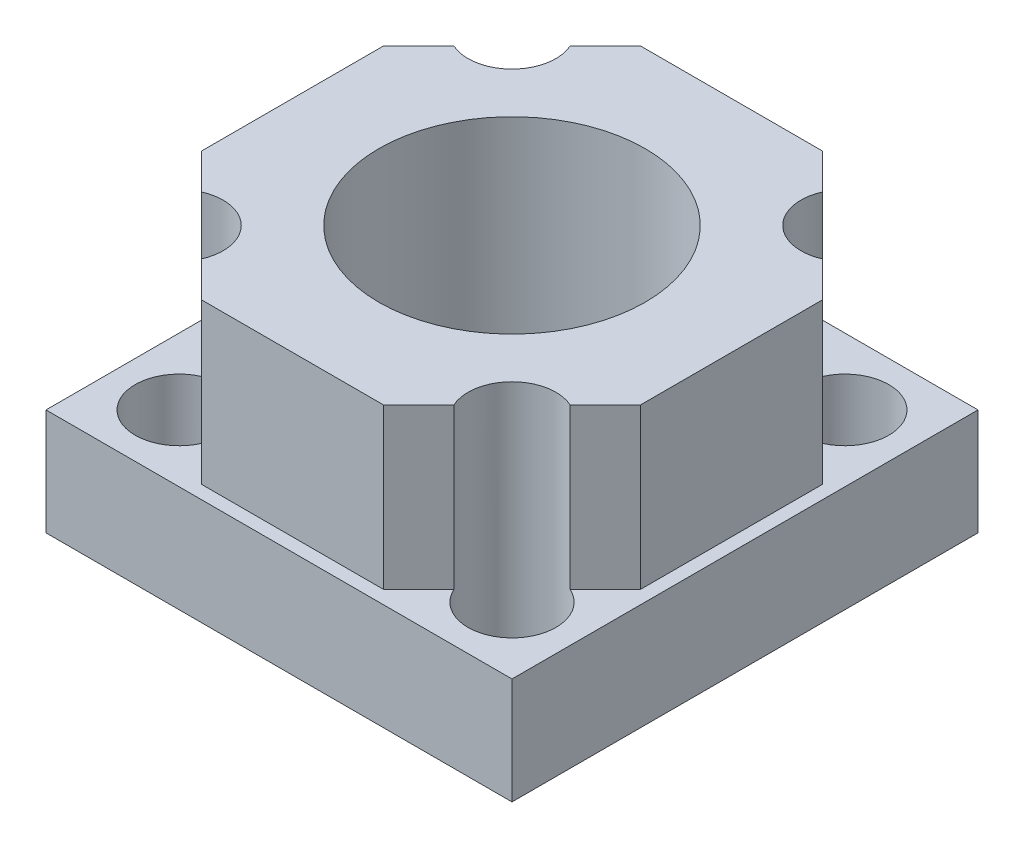
SolidWorks part; units mm, degrees
ref_plane "Front Plane" through (0, 0, 0) normal (0, 0, 1) x (1, 0, 0)
ref_plane "Top Plane" through (0, 0, 0) normal (0, 1, 0) x (1, 0, 0)
ref_plane "Right Plane" through (0, 0, 0) normal (1, 0, 0) x (0, 0, -1)
sketch "Sketch1" plane through (0, 0, 0) normal (0, 1, 0) x (1, 0, 0)
  line L0 (-16.5, -6.8345) -> (-6.8345, -16.5)
  line L1 (-17.5, 17.5) -> (17.5, 17.5)
  line L2 (-17.5, 17.5) -> (-17.5, -17.5)
  line L3 (-17.5, -17.5) -> (17.5, -17.5)
  line L4 (17.5, 17.5) -> (17.5, -17.5)
  line L5 (0, -17.5) -> (0, 17.5) construction
  line L6 (-17.5, 0) -> (17.5, 0) construction
  line L7 (6.8345, -16.5) -> (16.5, -6.8345)
  line L8 (16.5, -6.8345) -> (16.5, 6.8345)
  line L9 (16.5, 6.8345) -> (6.8345, 16.5)
  line L10 (6.8345, 16.5) -> (-6.8345, 16.5)
  line L11 (-6.8345, 16.5) -> (-16.5, 6.8345)
  line L12 (-16.5, 6.8345) -> (-16.5, -6.8345)
  line L13 (-6.8345, -16.5) -> (6.8345, -16.5)
  circle A0 centre (0, 0) radius 16.5 construction
  point P0 (0, 0)
  point P17 (16.5, 0)
  dimension "D1" = 35
  dimension "D2" = 35
  dimension "D3" = 33
extrude "Boss-Extrude1" add sketch "Sketch1" against normal blind 8 contours L0 L13 L7 L8 L9 L10 L11 L12 | L4 L1 L2 L3 L13 L0 L12 L11 L10 L9 L8 L7 region at (0, 0, 0) region at (0, 0, -17.005)
extrude "Boss-Extrude2" add sketch "Sketch1<3>" along normal blind 12 contours L0 L13 L7 L8 L9 L10 L11 L12 region at (0, 0, 0)
sketch "Sketch1<3>" plane through (0, 0, 0) normal (0, 1, 0) x (1, 0, 0) same geometry as "Sketch1"
hole_wizard "M18 Clearance Hole1" positions "Sketch2" profile "Sketch3" hole size "M18" standard "ISO" end condition through all
sketch "Sketch2" plane through (0, 12, 0) normal (0, 1, 0) x (1, 0, 0)
  point P0 (0, 0)
sketch "Sketch3" plane through (0, 12, 0) normal (1, 0, 0) x (0, 0, 1)
  line L0 (0, 0) -> (0, 20)
  line L1 (0, 20) -> (10, 20)
  line L2 (10, 20) -> (10, 0)
  line L5 (10, 0) -> (0, 0)
  line L11 (0, -6.35) -> (0, 107.95) construction
  dimension "Thru Hole Dia." = 20
  dimension "Thru Hole Depth" = 20
hole_wizard "M6 Clearance Hole1" positions "Sketch4" profile "Sketch5" hole size "M6" standard "ISO" end condition through all
sketch "Sketch4" plane through (0, 0, 0) normal (0, 1, 0) x (1, 0, 0)
  line L0 (-17.5, 17.5) -> (-17.5, -17.5) construction
  line L1 (-17.5, 17.5) -> (17.5, 17.5) construction
  point P0 (-12.5, 12.5)
  dimension "D1" = 5
  dimension "D2" = 5
sketch "Sketch5" plane through (-12.5, 0, -12.5) normal (1, 0, 0) x (0, 0, 1)
  line L0 (0, 0) -> (0, 8)
  line L1 (0, 8) -> (3.3, 8)
  line L2 (3.3, 8) -> (3.3, 0)
  line L5 (3.3, 0) -> (0, 0)
  line L11 (0, -6.35) -> (0, 107.95) construction
  dimension "Thru Hole Dia." = 6.6
  dimension "Thru Hole Depth" = 8
sketch "Sketch6" plane through (0, 0, 0) normal (0, -1, 0) x (1, 0, 0)
  line L1 (-13.8471, -9.4875) -> (-9.4875, -13.8471)
  line L2 (-13.8471, -9.4875) -> (-9.4875, -13.8471)
  arc A1 (-9.4875, -13.8471) -> (-13.8471, -9.4875) centre (-12.5, -12.5) ccw
  arc A2 (-9.4875, -13.8471) -> (-13.8471, -9.4875) centre (-12.5, -12.5) ccw
  dimension "D1" = 0
extrude "Cut-Extrude1" cut sketch "Sketch6" against normal through all
mirror "Mirror4" about plane through (0, 0, 0) normal (1, 0, 0) of "M6 Clearance Hole1"
mirror "Mirror5" about plane through (0, 0, 0) normal (0, 0, 1) of "Mirror4", "M6 Clearance Hole1"
sketch "Sketch7" plane through (0, 0, 0) normal (0, -1, 0) x (1, 0, 0)
  line L1 (-9.4875, 13.8471) -> (-13.8471, 9.4875)
  line L2 (-9.4875, 13.8471) -> (-13.8471, 9.4875)
  line L3 (13.8471, 9.4875) -> (9.4875, 13.8471)
  line L4 (13.8471, 9.4875) -> (9.4875, 13.8471)
  line L5 (9.4875, -13.8471) -> (13.8471, -9.4875)
  line L6 (9.4875, -13.8471) -> (13.8471, -9.4875)
  arc A1 (-13.8471, 9.4875) -> (-9.4875, 13.8471) centre (-12.5, 12.5) ccw
  arc A2 (-13.8471, 9.4875) -> (-9.4875, 13.8471) centre (-12.5, 12.5) ccw
  arc A3 (9.4875, 13.8471) -> (13.8471, 9.4875) centre (12.5, 12.5) ccw
  arc A4 (9.4875, 13.8471) -> (13.8471, 9.4875) centre (12.5, 12.5) ccw
  arc A5 (13.8471, -9.4875) -> (9.4875, -13.8471) centre (12.5, -12.5) ccw
  arc A6 (13.8471, -9.4875) -> (9.4875, -13.8471) centre (12.5, -12.5) ccw
  dimension "D1" = 0
  dimension "D2" = 0
  dimension "D3" = 0
extrude "Cut-Extrude2" cut sketch "Sketch7" against normal through all
